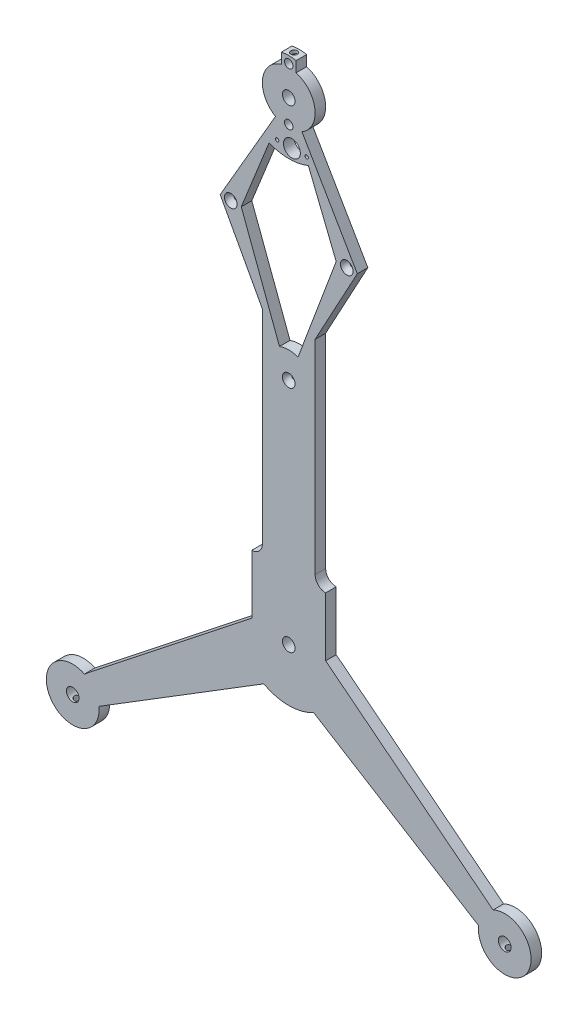
SolidWorks part; units mm, degrees
ref_plane "Front Plane" through (0, 0, 0) normal (0, 0, 1) x (1, 0, 0)
ref_plane "Top Plane" through (0, 0, 0) normal (0, 1, 0) x (1, 0, 0)
ref_plane "Right Plane" through (0, 0, 0) normal (1, 0, 0) x (0, 0, -1)
sketch "Sketch1" plane through (0, 0, 0) normal (0, 0, 1) x (1, 0, 0)
  line L1 (0, -108.5) -> (0, -78.5) construction
  line L2 (-12.5, 0) -> (-12.5, -98.5) construction
  line L3 (12.5, 0) -> (-12.5, 0) construction
  line L6 (-12.5, 0) -> (-12.5, -78.5)
  line L7 (0, 0) -> (-12.5, 0) construction
  line L8 (-17.5, -106.385) -> (-96.8528, -168.9924)
  line L9 (-102.394, -180.1971) -> (0, -108.5) construction
  line L10 (-96.8528, -168.9924) -> (-93.4113, -173.9073) construction
  line L11 (0, -133.5) -> (0, -108.5)
  line L15 (-17.5, -78.5) -> (-17.5, -106.385)
  line L16 (-12.5, -78.5) -> (-17.5, -78.5)
  line L17 (0, -108.5) -> (0, 0)
  line L18 (-11.8417, -130.5176) -> (-89.9698, -178.8222)
  line L19 (0, 0) -> (0, 12.5)
  circle A1 centre (-102.394, -180.1971) radius 12.5 construction
  arc A2 (-96.8528, -168.9924) -> (-89.9698, -178.8222) centre (-102.394, -180.1971) ccw
  circle A3 centre (0, -108.5) radius 12.5 construction
  arc A4 (-11.8417, -130.5176) -> (0, -133.5) centre (0, -108.5) ccw
  arc A5 (0, 12.5) -> (-12.5, 0) centre (0, 0) ccw
  dimension "D1" = 30
  dimension "D2" = 25
  dimension "D3" = 6
  dimension "D6" = 25
  dimension "D4" = 5
extrude "Boss-Extrude1" add sketch "Sketch1" along normal up to vertex (5 mm away)
sketch "Sketch3" plane through (0, 0, 0) normal (0, 0, 1) x (1, 0, 0)
  line L0 (-27.5, 59.9979) -> (0, 0) construction
  line L1 (0, 115.9979) -> (-27.5, 59.9979) construction
  line L2 (-32.5, 59.9979) -> (-22.5, 59.9979) construction
  line L3 (-22.5, 59.9979) -> (0, 0)
  line L4 (-32.5, 59.9979) -> (-12.5, 23.0761)
  line L5 (-12.5, 23.0761) -> (0, 0) construction
  line L6 (-9.3205, 92.8003) -> (-22.5, 59.9979)
  line L7 (-6.2744, 105.1867) -> (-32.5, 59.9979)
  line L8 (-12.5, 23.0761) -> (-12.5, 0)
  line L9 (0, 0) -> (-12.5, 0)
  line L10 (0, 115.9979) -> (0, 90.9979)
  line L11 (0, 115.9979) -> (0, 128.4979)
  arc A1 (0, 128.4979) -> (-6.2744, 105.1867) centre (0, 115.9979) ccw
  arc A2 (-9.3205, 92.8003) -> (0, 90.9979) centre (0, 115.9979) ccw
  circle A3 centre (0, 0) radius 12.5 construction
  point P0 (-27.5, 59.9979)
  point P1 (0, 0)
  point P3 (27.5, 59.9979)
  point P5 (0, 115.9979)
  point P14 (-27.5, 59.9979)
  dimension "D2" = 25
  dimension "D1" = 10
extrude "Boss-Extrude2" add sketch "Sketch3" along normal up to surface (5 mm away) up to face at (-31.1845, -97.1469, 5)
fillet "Fillet2" radius 5 1 edges at (-12.5, -78.5, 2.5)
mirror "Mirror1" about plane through (0, -133.5, 5) normal (-1, 0, 0) of bodies 117
sketch "Sketch2" plane through (0, 0, 5) normal (0, 0, 1) x (1, 0, 0)
  circle A0 centre (0, -108.5) radius 3 construction
  circle A1 centre (0, -108.5) radius 3
extrude "Cut-Extrude1" cut sketch "Sketch2" against normal through all
sketch "Sketch4" plane through (0, 0, 5) normal (0, 0, 1) x (1, 0, 0)
  circle A0 centre (-102.394, -180.1971) radius 3 construction
  circle A1 centre (-102.394, -180.1971) radius 3
  circle A2 centre (102.394, -180.1971) radius 3
  circle A3 centre (0, 115.9979) radius 3
extrude "Cut-Extrude2" cut sketch "Sketch4" against normal through all
sketch "Sketch5" plane through (0, 0, 5) normal (0, 0, 1) x (1, 0, 0)
  circle A0 centre (0, 0) radius 1.25 construction
  circle A1 centre (0, 0) radius 1.25
extrude "Cut-Extrude3" cut sketch "Sketch5" against normal through all
sketch "Sketch7" plane through (0, 0, 0) normal (1, 0, 0) x (0, 0, -1)
  line L0 (-5, 0) -> (-2, 0)
  line L1 (-5, 0) -> (-5, -3)
  line L2 (-5, 23.0761) -> (-5, -73.5) construction
  arc A0 (-2, 0) -> (-5, -3) centre (-5, 0) cw
  dimension "D1" = 3
revolve "Cut-Revolve2" cut sketch "Sketch7" angle 360 about L0
sketch "Sketch8" plane through (0, 0, 0) normal (0, 0, -1) x (-1, 0, 0)
  circle A0 centre (-27.5, 59.9979) radius 1.25
  circle A1 centre (27.5, 59.9979) radius 1.25
  circle A2 centre (0, 0) radius 1.25 construction
extrude "Cut-Extrude4" cut sketch "Sketch8" against normal through all
sketch "Sketch9" plane through (0, 0, 5) normal (0, 0, 1) x (1, 0, 0)
  circle A0 centre (0, -40) radius 1.25 construction
  circle A1 centre (0, -40) radius 1.25
extrude "Cut-Extrude5" [suppressed] cut sketch "Sketch9" against normal through all
sketch "Sketch10" plane through (0, 0, 5) normal (0, 0, 1) x (1, 0, 0)
  circle A0 centre (0, -80.5) radius 1 construction
  circle A1 centre (0, -80.5) radius 1
extrude "Cut-Extrude6" [suppressed] cut sketch "Sketch10" against normal through all
sketch "Sketch11" plane through (0, 0, 5) normal (0, 0, 1) x (1, 0, 0)
  circle A0 centre (6, -33) radius 0.5 construction
  circle A1 centre (6, -45) radius 1 construction
  circle A2 centre (6, -33) radius 0.5
  circle A3 centre (6, -45) radius 1
extrude "Cut-Extrude7" [suppressed] cut sketch "Sketch11" against normal through all
hole_wizard "M2x0.4 Tapped Hole1" [suppressed] positions "Sketch12" profile "Sketch13" tap size "M2x0.4" standard "ANSI Metric"
sketch "Sketch12" plane through (0, 0, 5) normal (0, 0, 1) x (1, 0, 0)
  point P6 (-15.9651, 83.4872)
  point P9 (15.9651, 83.4872)
sketch "Sketch13" plane through (-15.9651, 83.4872, 5) normal (1, 0, 0) x (0, -1, 0)
  line L0 (0, 0) -> (0, 5)
  line L1 (0, 5) -> (0.8, 5)
  line L2 (0.8, 5) -> (0.8, 0)
  line L5 (0.8, 0) -> (0, 0)
  line L11 (0, -6.35) -> (0, 107.95) construction
  dimension "Thru Tap Drill Dia." = 1.6
  dimension "Thru Tap Drill Depth" = 5
cosmetic thread "Hole Thread1" [suppressed] parameters "D1"=5, "D2"=2
cosmetic thread "Hole Thread2" [suppressed] parameters "D1"=5, "D2"=2
sketch "Sketch14" plane through (0, 0, 5) normal (0, 0, 1) x (1, 0, 0)
  line L0 (-3.5, 127.9979) -> (3.5, 127.9979) construction
  line L1 (-3.5, 132.9979) -> (-3.5, 127.9979) construction
  line L2 (3.5, 127.9979) -> (3.5, 132.9979) construction
  line L3 (-3.5, 127.9979) -> (3.5, 127.9979)
  line L4 (-3.5, 132.9979) -> (-3.5, 127.9979)
  line L5 (3.5, 127.9979) -> (3.5, 132.9979)
  arc A0 (3.5, 132.9979) -> (-3.5, 132.9979) centre (0, 115.9979) ccw construction
  arc A1 (3.5, 132.9979) -> (-3.5, 132.9979) centre (0, 115.9979) ccw
extrude "Boss-Extrude3" add sketch "Sketch14" against normal up to surface (5 mm away) up to face at (26.25, 59.9979, 0)
sketch "Sketch15" plane through (0, 0, 5) normal (0, 0, 1) x (1, 0, 0)
  circle A0 centre (0, 104.9979) radius 2 construction
  circle A1 centre (0, 129.9979) radius 2 construction
  circle A2 centre (0, 104.9979) radius 2
  circle A3 centre (0, 129.9979) radius 2
extrude "Cut-Extrude8" cut sketch "Sketch15" against normal through all
sketch "Sketch16" plane through (0, 0, 0) normal (0, 0, 1) x (1, 0, 0)
  line L0 (-14.2654, 133.3545) -> (15.6334, 133.3545)
  arc A0 (3.5, 132.9979) -> (-3.5, 132.9979) centre (0, 115.9979) ccw construction
ref_plane "Plane1" through (0, 133.3545, 0) normal (0, 1, 0) x (1, 0, 0)
sketch "Sketch17" plane through (0, 133.3545, 0) normal (0, 1, 0) x (1, 0, 0)
  line L0 (0, 0) -> (0, -5) construction
  line L1 (-3.5, -5) -> (3.5, -5) construction
  circle A0 centre (0, -2.5) radius 1.5
  dimension "D1" = 3
extrude "Cut-Extrude9" cut sketch "Sketch17" against normal blind 3
sketch "Sketch18" plane through (0, 0, 5) normal (0, 0, 1) x (1, 0, 0)
  circle A0 centre (0, 95.9979) radius 1.25 construction
  circle A1 centre (0, 95.9979) radius 1.25
extrude "Cut-Extrude10" [suppressed] cut sketch "Sketch18" against normal through all
sketch "Sketch19" plane through (0, 0, 5) normal (0, 0, 1) x (1, 0, 0)
  circle A3 centre (1.5, 95.9979) radius 4 construction
  circle A4 centre (1.5, 95.9979) radius 4
extrude "Cut-Extrude11" cut sketch "Sketch19" against normal through all
hole_wizard "M2x0.4 Tapped Hole2" positions "Sketch20" profile "Sketch21" tap size "M2x0.4" standard "ANSI Metric" end condition through all
sketch "Sketch20" plane through (0, 0, 0) normal (0, 0, 1) x (1, 0, 0)
  circle A1 centre (1.5, 95.9979) radius 7
  point P0 (8.5, 95.9979)
  point P16 (-5.5, 95.9979)
  dimension "D1" = 14
sketch "Sketch21" plane through (8.5, 95.9979, 0) normal (1, 0, 0) x (0, 1, 0)
  line L0 (0, 0) -> (0, 5)
  line L1 (0, 5) -> (0.8, 5)
  line L2 (0.8, 5) -> (0.8, 0)
  line L5 (0.8, 0) -> (0, 0)
  line L11 (0, -6.35) -> (0, 107.95) construction
  dimension "Thru Tap Drill Dia." = 1.6
  dimension "Thru Tap Drill Depth" = 5
cosmetic thread "Hole Thread3" parameters "D2"=2
cosmetic thread "Hole Thread4" parameters "D2"=2
sketch "Sketch22" plane through (0, 0, 5) normal (0, 0, 1) x (1, 0, 0)
  point P0 (27.5, 59.9979)
  point P1 (-27.5, 59.9979)
pattern_sketch "Sketch-Pattern1" of "Cut-Revolve2" driven by "Sketch22"
sketch "Sketch23" [suppressed] plane through (0, 0, 5) normal (0, 0, 1) x (1, 0, 0)
  point P0 (0, 96.2376)
pattern_sketch "Sketch-Pattern2" [suppressed]
sketch "Sketch24" plane through (0, 0, 0) normal (0, 0, 1) x (1, 0, 0)
  line L0 (-102.394, -192.6971) -> (102.394, -192.6971)
  arc A0 (-96.8528, -168.9924) -> (-89.9698, -178.8222) centre (-102.394, -180.1971) ccw construction
  arc A1 (89.9698, -178.8222) -> (96.8528, -168.9924) centre (102.394, -180.1971) ccw construction
ref_plane "Plane2" through (0, -192.6971, 0) normal (0, 1, 0) x (1, 0, 0)
hole_wizard "M4x0.7 Tapped Hole1" positions "Sketch26" profile "Sketch27" tap size "M4x0.7" standard "ANSI Metric"
sketch "Sketch26" plane through (0, -192.6971, 0) normal (0, 1, 0) x (1, 0, 0)
  line L0 (114.894, -5) -> (114.894, 0) construction
  line L1 (114.894, -5) -> (114.894, 0)
  point P0 (102.394, -2.5)
  point P6 (114.894, -2.5)
  point P7 (-102.394, -2.5)
sketch "Sketch27" plane through (102.394, -192.6971, 2.5) normal (1, 0, 0) x (0, 0, -1)
  line L0 (0, 0) -> (0, 12.4914)
  line L1 (0, 12.4914) -> (1.65, 11.5)
  line L2 (1.65, 11.5) -> (1.65, 0)
  line L5 (1.65, 0) -> (0, 0)
  line L10 (0, 12.4914) -> (-1.65, 11.5) construction
  line L11 (0, -6.35) -> (0, 107.95) construction
  dimension "Tap Drill Dia." = 3.3
  dimension "Tap Drill Depth" = 11.5
  dimension "Drill Angle" = 118
cosmetic thread "Hole Thread5" parameters "D1"=8, "D2"=4
cosmetic thread "Hole Thread6" parameters "D1"=8, "D2"=4
